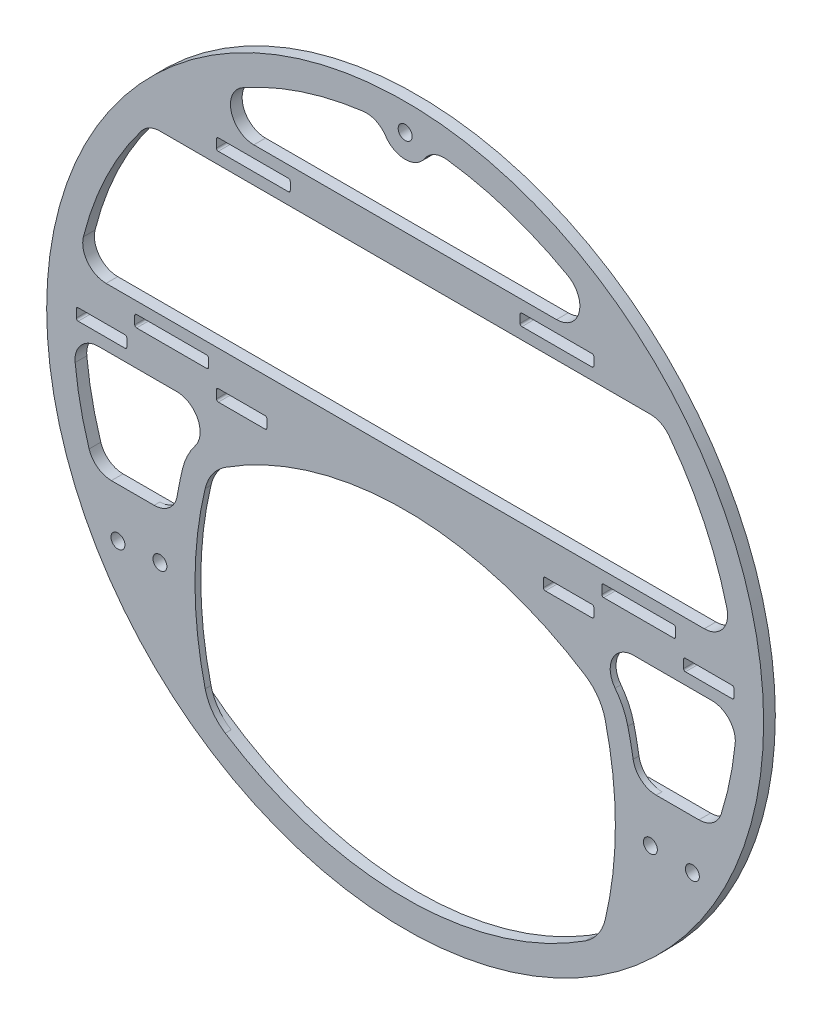
SolidWorks part; units mm, degrees
ref_plane "Front Plane" through (0, 0, 0) normal (0, 0, 1) x (1, 0, 0)
ref_plane "Top Plane" through (0, 0, 0) normal (0, 1, 0) x (1, 0, 0)
ref_plane "Right Plane" through (0, 0, 0) normal (1, 0, 0) x (0, 0, -1)
sketch "Sketch1" plane through (0, 0, 0) normal (0, 0, 1) x (1, 0, 0)
  circle A0 centre (0, 0) radius 97.4725
  circle A1 centre (0, 0) radius 90.17
  dimension "D1" = 194.945
  dimension "D2" = 180.34
extrude "Boss-Extrude1" add sketch "Sketch1" along normal mid plane 3.175
sketch "Sketch2" plane through (0, 0, 1.5875) normal (0, 0, 1) x (1, 0, 0)
  arc A5 (-5.2915, 86.6596) -> (5.2915, 86.6596) centre (0, 90.17) ccw
  circle A6 centre (0, 0) radius 90.17 construction
  arc A8 (-5.2915, 86.6596) -> (-11.3847, 89.4484) centre (-10.5829, 83.1492) ccw
  arc A9 (5.2915, 86.6596) -> (11.3847, 89.4484) centre (10.5829, 83.1492) cw
  arc A10 (11.3847, 89.4484) -> (-11.3847, 89.4484) centre (0, 0) ccw
  dimension "D3" = 6.35
  dimension "D4" = 6.35
extrude "Boss-Extrude2" add sketch "Sketch2" against normal up to surface (3.175 mm away) up to face at (97.4725, 0, -1.5875)
hole_wizard "#6 Clearance Hole2" positions "Sketch8" profile "Sketch7" hole size "#6" standard "ANSI Inch"
sketch "Sketch8" plane through (0, 0, -1.5875) normal (0, 0, -1) x (-1, 0, 0)
  point P0 (0, 90.17)
sketch "Sketch7" plane through (0, 90.17, -1.5875) normal (1, 0, 0) x (0, 1, 0)
  line L0 (0, 0) -> (0, 7.4908)
  line L1 (0, 7.4908) -> (1.8986, 6.35)
  line L2 (1.8986, 6.35) -> (1.8986, 0)
  line L5 (1.8986, 0) -> (0, 0)
  line L10 (0, 7.4908) -> (-1.8987, 6.35) construction
  line L11 (0, -6.35) -> (0, 107.95) construction
  dimension "Hole Dia." = 3.7973
  dimension "Hole Depth" = 6.35
  dimension "Drill Angle" = 118
pattern_circular "CirPattern2" count 3 over 360 about axis through (0, 0, -1.5875) along (0, 0, 1) of "#6 Clearance Hole2", "Boss-Extrude2"
sketch "Sketch9" plane through (0, 0, 0) normal (0, 0, 1) x (1, 0, 0)
  line L0 (44.45, -44.45) -> (-44.45, -44.45) construction
  line L1 (0, 0) -> (0, 50000) construction
  arc A0 (48.9116, -13.1485) -> (-48.9116, -13.1485) centre (0, -88.9) ccw
  arc A1 (-54.3759, -20.8703) -> (-54.3759, -68.0297) centre (44.45, -44.45) ccw
  arc A2 (-48.9116, -75.7515) -> (48.9116, -75.7515) centre (0, 0) ccw
  arc A3 (-48.9116, -75.7515) -> (-54.3759, -68.0297) centre (-42.0227, -65.0822) cw
  arc A4 (48.9116, -75.7515) -> (54.3759, -68.0297) centre (42.0227, -65.0822) ccw
  arc A5 (54.3759, -68.0297) -> (54.3759, -20.8703) centre (-44.45, -44.45) ccw
  arc A6 (48.9116, -13.1485) -> (54.3759, -20.8703) centre (42.0227, -23.8178) cw
  arc A7 (-48.9116, -13.1485) -> (-54.3759, -20.8703) centre (-42.0227, -23.8178) ccw
  arc A8 (-71.7723, -54.5836) -> (71.7723, -54.5836) centre (0, 0) ccw construction
  arc A9 (60.5525, -69.5034) -> (60.5525, -19.3966) centre (-44.45, -44.45) ccw
  arc A10 (52.3561, -7.8139) -> (60.5525, -19.3966) centre (42.0227, -23.8178) cw
  arc A11 (52.3561, -7.8139) -> (-52.3561, -7.8139) centre (0, -88.9) ccw
  arc A12 (-52.3561, -7.8139) -> (-60.5525, -19.3966) centre (-42.0227, -23.8178) ccw
  arc A13 (-60.5525, -19.3966) -> (-60.5525, -69.5034) centre (44.45, -44.45) ccw
  arc A14 (-52.3561, -81.0861) -> (-60.5525, -69.5034) centre (-42.0227, -65.0822) cw
  arc A15 (-52.3561, -81.0861) -> (52.3561, -81.0861) centre (0, 0) ccw
  arc A16 (52.3561, -81.0861) -> (60.5525, -69.5034) centre (42.0227, -65.0822) ccw
  dimension "D1" = 12.7
  dimension "D4" = 101.6
  dimension "D2" = 44.45
  dimension "D3" = 88.9
  dimension "D5" = 6.35
extrude "Boss-Extrude3" add sketch "Sketch9" along normal up to surface (1.5875 mm away) up to face at (79.9882, -45.085, 1.5875)
sketch "Sketch10" plane through (0, 0, 1.5875) normal (0, 0, 1) x (1, 0, 0)
  line L0 (-84.3953, -31.75) -> (-62.7503, -31.75)
  line L1 (62.7503, -31.75) -> (84.3953, -31.75)
  arc A8 (-11.3847, 89.4484) -> (-83.1569, -34.8648) centre (0, 0) ccw construction
  arc A9 (-60.5525, -19.3966) -> (-61.3011, -66.1271) centre (44.45, -44.45) ccw construction
  arc A14 (61.3011, -66.1271) -> (60.5525, -19.3966) centre (-44.45, -44.45) ccw construction
  arc A15 (83.1569, -34.8648) -> (11.3847, 89.4484) centre (0, 0) ccw construction
  arc M9 (-60.5525, -19.3966) -> (-61.3011, -66.1271) centre (44.45, -44.45) ccw
  arc M11 (-61.3011, -66.1271) -> (-71.7723, -54.5836) centre (0, 0) cw
  arc M12 (-71.7723, -54.5836) -> (-72.4037, -47.9124) centre (-66.7179, -50.7397) cw
  arc M13 (-72.4037, -47.9124) -> (-77.6952, -38.7473) centre (-78.0895, -45.085) ccw
  arc M14 (-77.6952, -38.7473) -> (-83.1569, -34.8648) centre (-77.3008, -32.4095) cw
  arc M15 (-83.1569, -34.8648) -> (-11.3847, 89.4484) centre (0, 0) cw
  arc M19 (11.3847, 89.4484) -> (83.1569, -34.8648) centre (0, 0) cw
  arc M20 (83.1569, -34.8648) -> (77.6952, -38.7473) centre (77.3008, -32.4095) cw
  arc M21 (77.6952, -38.7473) -> (72.4037, -47.9124) centre (78.0895, -45.085) ccw
  arc M22 (72.4037, -47.9124) -> (71.7723, -54.5836) centre (66.7179, -50.7397) cw
  arc M23 (71.7723, -54.5836) -> (61.3011, -66.1271) centre (0, 0) cw
  arc M25 (61.3011, -66.1271) -> (60.5525, -19.3966) centre (-44.45, -44.45) ccw
  dimension "D1" = 31.75
extrude "Boss-Extrude4" add sketch "Sketch10" against normal up to surface (3.175 mm away) contours L0 M15 M14 M13 M12 M11 M9 | L1 M25 M23 M22 M21 M20 M19 region at (-69.6294, -43.7845, 1.5875) region at (69.6294, -43.7845, 1.5875)
fillet "Fillet2" radius 6.35 4 edges at (84.3953, -31.75, 0) (62.7503, -31.75, 0.7937) (-84.3953, -31.75, 0) (-62.7503, -31.75, 0.7937)
hole_wizard "#6 Clearance Hole1" positions "Sketch12" profile "Sketch11" hole size "#6" standard "ANSI Inch" end condition through all
sketch "Sketch12" plane through (0, 0, 1.5875) normal (0, 0, 1) x (1, 0, 0)
  line L0 (0, 0) -> (0, -50000) construction
  arc A0 (-54.3759, -20.8703) -> (-54.3759, -68.0297) centre (44.45, -44.45) ccw construction
  arc A1 (-54.3759, -20.8703) -> (-54.3759, -68.0297) centre (44.45, -44.45) ccw construction
  point P0 (-66.675, -44.45)
  point P2 (66.675, -44.45)
  point P9 (-57.15, -44.45)
  point P10 (-57.15, -44.45)
  dimension "D1" = 9.525
sketch "Sketch11" plane through (-66.675, -44.45, 1.5875) normal (1, 0, 0) x (0, -1, 0)
  line L0 (0, 0) -> (0, 3.175)
  line L1 (0, 3.175) -> (1.8986, 3.175)
  line L2 (1.8986, 3.175) -> (1.8986, 0)
  line L5 (1.8986, 0) -> (0, 0)
  line L11 (0, -6.35) -> (0, 107.95) construction
  dimension "Thru Hole Dia." = 3.7973
  dimension "Thru Hole Depth" = 3.175
sketch "Sketch13" plane through (0, 0, 1.5875) normal (0, 0, 1) x (1, 0, 0)
  line L0 (-90.1499, -1.905) -> (90.1499, -1.905)
  line L1 (-89.8475, 7.62) -> (89.8475, 7.62)
  line L2 (0, 0) -> (0, 50000) construction
  line L3 (-89.408, 4.445) -> (-75.692, 4.445)
  line L4 (-89.408, 4.445) -> (-89.408, 1.27)
  line L5 (-89.408, 1.27) -> (-75.692, 1.27)
  line L6 (-75.692, 4.445) -> (-75.692, 1.27)
  line L8 (89.408, 1.27) -> (75.692, 1.27)
  line L9 (89.408, 1.27) -> (89.408, 4.445)
  line L10 (89.408, 4.445) -> (75.692, 4.445)
  line L11 (75.692, 1.27) -> (75.692, 4.445)
  line L12 (-51.308, 4.445) -> (-37.592, 4.445)
  line L13 (-51.308, 4.445) -> (-51.308, 1.27)
  line L14 (-51.308, 1.27) -> (-37.592, 1.27)
  line L15 (-37.592, 4.445) -> (-37.592, 1.27)
  line L16 (51.308, 4.445) -> (37.592, 4.445)
  line L17 (51.308, 4.445) -> (51.308, 1.27)
  line L18 (51.308, 1.27) -> (37.592, 1.27)
  line L19 (37.592, 4.445) -> (37.592, 1.27)
  arc A0 (-11.3847, 89.4484) -> (-85.9303, -27.3242) centre (0, 0) ccw construction
  arc A1 (85.9303, -27.3242) -> (11.3847, 89.4484) centre (0, 0) ccw construction
  arc A2 (-89.8475, 7.62) -> (-90.1499, -1.905) centre (0, 0) ccw
  arc A3 (90.1499, -1.905) -> (89.8475, 7.62) centre (0, 0) ccw
  point P27 (-82.55, 4.445)
  point P28 (82.55, 4.445)
  point P29 (-82.55, 1.27)
  point P30 (-44.45, 1.27)
  point P31 (44.45, 1.27)
  point P32 (82.55, 1.27)
  dimension "D1" = 9.525
  dimension "D2" = 1.905
  dimension "D3" = 3.175
  dimension "D4" = 3.175
  dimension "D5" = 13.716
  dimension "D6" = 165.1
  dimension "D7" = 38.1
  dimension "D8" = 38.1
extrude "Boss-Extrude5" add sketch "Sketch13" against normal up to surface (3.175 mm away)
sketch "Sketch14" plane through (0, 0, 1.5875) normal (0, 0, 1) x (1, 0, 0)
  line L0 (-23.7171, -1.905) -> (23.7171, -1.905)
  line L1 (-89.408, 1.27) -> (-75.692, 1.27)
  line L2 (-89.408, 1.27) -> (-89.408, 4.445)
  line L3 (-89.408, 4.445) -> (-75.692, 4.445)
  line L4 (-75.692, 1.27) -> (-75.692, 4.445)
  line L5 (89.408, 1.27) -> (75.692, 1.27)
  line L6 (89.408, 1.27) -> (89.408, 4.445)
  line L7 (89.408, 4.445) -> (75.692, 4.445)
  line L8 (75.692, 1.27) -> (75.692, 4.445)
  arc A0 (23.7171, -1.905) -> (-23.7171, -1.905) centre (0, -88.9) ccw
  arc A1 (-23.7171, -1.905) -> (-48.9116, -13.1485) centre (0, -88.9) ccw construction
extrude "Cut-Extrude1" cut sketch "Sketch14" against normal through all
sketch "Sketch15" plane through (0, 0, 1.5875) normal (0, 0, 1) x (1, 0, 0)
  line L0 (89.0812, 13.97) -> (-89.0812, 13.97)
  line L1 (-89.8475, 7.62) -> (89.8475, 7.62) construction
  line L2 (-89.8475, 7.62) -> (-73.533, 7.62)
  line L4 (0, 0) -> (0, 50000) construction
  line L5 (73.533, 10.795) -> (53.467, 10.795)
  line L6 (73.533, 10.795) -> (73.533, 7.62)
  line L7 (73.533, 7.62) -> (89.8475, 7.62)
  line L8 (53.467, 10.795) -> (53.467, 7.62)
  line L9 (-53.467, 10.795) -> (-73.533, 10.795)
  line L10 (-53.467, 10.795) -> (-53.467, 7.62)
  line L12 (-73.533, 10.795) -> (-73.533, 7.62)
  line L13 (-53.467, 7.62) -> (53.467, 7.62)
  arc A0 (89.8475, 7.62) -> (11.3847, 89.4484) centre (0, 0) ccw construction
  arc A1 (-11.3847, 89.4484) -> (-89.8475, 7.62) centre (0, 0) ccw construction
  arc A2 (89.8475, 7.62) -> (89.0812, 13.97) centre (0, 0) ccw
  arc A3 (-89.0812, 13.97) -> (-89.8475, 7.62) centre (0, 0) ccw
  point P15 (-63.5, 10.795)
  point P18 (63.5, 10.795)
  dimension "D1" = 6.35
  dimension "D2" = 3.175
  dimension "D3" = 127
  dimension "D4" = 20.066
extrude "Boss-Extrude6" add sketch "Sketch15" against normal up to surface (3.175 mm away)
sketch "Sketch16" plane through (0, 0, 1.5875) normal (0, 0, 1) x (1, 0, 0)
  line L0 (-60.7048, 66.675) -> (60.7048, 66.675)
  line L1 (-69.746, 57.15) -> (69.746, 57.15)
  line L2 (0, 0) -> (0, 50000) construction
  line L3 (-51.308, 63.5) -> (-31.242, 63.5)
  line L4 (-51.308, 63.5) -> (-51.308, 60.325)
  line L5 (-51.308, 60.325) -> (-31.242, 60.325)
  line L6 (-31.242, 63.5) -> (-31.242, 60.325)
  line L7 (31.242, 60.325) -> (51.308, 60.325)
  line L8 (31.242, 60.325) -> (31.242, 63.5)
  line L9 (31.242, 63.5) -> (51.308, 63.5)
  line L10 (51.308, 60.325) -> (51.308, 63.5)
  arc A0 (-11.3847, 89.4484) -> (-89.0812, 13.97) centre (0, 0) ccw construction
  arc A1 (89.0812, 13.97) -> (11.3847, 89.4484) centre (0, 0) ccw construction
  arc A2 (69.746, 57.15) -> (60.7048, 66.675) centre (0, 0) ccw
  arc A3 (-60.7048, 66.675) -> (-69.746, 57.15) centre (0, 0) ccw
  point P2 (-41.275, 63.5)
  point P20 (41.275, 63.5)
  dimension "D2" = 57.15
  dimension "D1" = 9.525
  dimension "D3" = 20.066
  dimension "D4" = 82.55
  dimension "D5" = 3.175
  dimension "D6" = 3.175
extrude "Boss-Extrude7" add sketch "Sketch16" against normal up to surface (3.175 mm away)
fillet "Fillet3" radius 6.35 10 edges at (90.1499, -1.905, 0) (-90.1499, -1.905, 0) (41.8089, -1.905, 0.7937) (-41.8089, -1.905, 0.7937) (-89.0812, 13.97, 0) (89.0812, 13.97, 0) (-69.746, 57.15, 0) (-60.7048, 66.675, 0) (69.746, 57.15, 0) (60.7048, 66.675, 0)
fillet "Fillet4" radius 0.508 32 edges at (-51.308, 63.5, 0) (-51.308, 60.325, 0) (-31.242, 60.325, 0) (-31.242, 63.5, 0) (31.242, 60.325, 0) (31.242, 63.5, 0) (51.308, 60.325, 0) (51.308, 63.5, 0) (-89.408, 4.445, 0) (-89.408, 1.27, 0) (-75.692, 1.27, 0) (-75.692, 4.445, 0) (-73.533, 10.795, 0) (-73.533, 7.62, 0) (-53.467, 7.62, 0) (-53.467, 10.795, 0) (-51.308, 4.445, 0) (-51.308, 1.27, 0) (-37.592, 1.27, 0) (-37.592, 4.445, 0) (37.592, 4.445, 0) (37.592, 1.27, 0) (51.308, 1.27, 0) (51.308, 4.445, 0) (53.467, 10.795, 0) (53.467, 7.62, 0) (75.692, 4.445, 0) (75.692, 1.27, 0) (89.408, 1.27, 0) (89.408, 4.445, 0) (73.533, 7.62, 0) (73.533, 10.795, 0)
